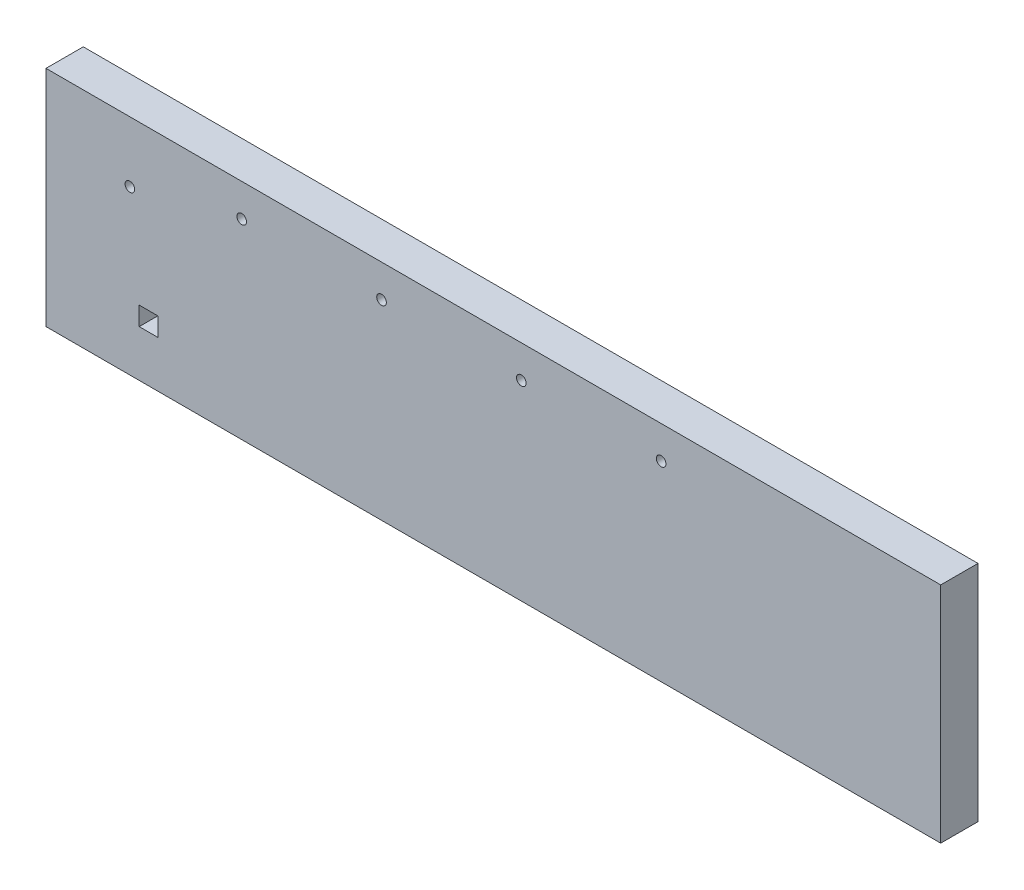
SolidWorks part; units mm, degrees
ref_plane "Front Plane" through (0, 0, 0) normal (0, 0, 1) x (1, 0, 0)
ref_plane "Top Plane" through (0, 0, 0) normal (0, 1, 0) x (1, 0, 0)
ref_plane "Right Plane" through (0, 0, 0) normal (1, 0, 0) x (0, 0, -1)
sketch "Sketch1" plane through (0, 0, 0) normal (0, 0, 1) x (1, 0, 0)
  line L1 (1219.2, 304.8) -> (-1219.2, 304.8)
  line L2 (1219.2, 304.8) -> (1219.2, -304.8)
  line L3 (1219.2, -304.8) -> (-1219.2, -304.8)
  line L4 (-1219.2, 304.8) -> (-1219.2, -304.8)
  line L5 (1219.2, 304.8) -> (-1219.2, -304.8) construction
  line L6 (1219.2, -304.8) -> (-1219.2, 304.8) construction
  line L7 (-965.2, -127) -> (-914.4, -127)
  line L8 (-965.2, -127) -> (-965.2, -177.8)
  line L9 (-965.2, -177.8) -> (-914.4, -177.8)
  line L10 (-914.4, -127) -> (-914.4, -177.8)
  line L11 (-965.2, -127) -> (-914.4, -177.8) construction
  line L12 (-965.2, -177.8) -> (-914.4, -127) construction
  circle A0 centre (-990.6, 139.7) radius 13.1198
  circle A1 centre (-685.8, 215.9) radius 13.1198
  circle A2 centre (-304.8, 215.9) radius 13.1198
  circle A3 centre (76.2, 215.9) radius 13.1198
  circle A4 centre (457.2, 215.9) radius 13.1198
  point P0 (0, 0)
  point P10 (-939.8, -152.4)
  dimension "D10" = 381
  dimension "D11" = 381
  dimension "D12" = 381
  dimension "D1" = 609.6
  dimension "D2" = 2438.4
  dimension "D3" = 88.9
  dimension "D4" = 228.6
  dimension "D5" = 304.8
  dimension "D6" = 165.1
  dimension "D7" = 127
  dimension "D8" = 50.8
  dimension "D9" = 254
extrude "Boss-Extrude1" add sketch "Sketch1" along normal blind 101.6
sketch "Sketch2" plane through (0, 0, 0) normal (0, 0, -1) x (-1, 0, 0)
  line L0 (1219.2, -304.8) -> (-1219.2, -304.8) construction
  line L1 (711.2, -288.925) -> (-711.2, -288.925)
  line L2 (711.2, -288.925) -> (711.2, -273.05)
  line L3 (711.2, -273.05) -> (-711.2, -273.05)
  line L4 (-711.2, -288.925) -> (-711.2, -273.05)
  line L5 (711.2, -288.925) -> (-711.2, -273.05) construction
  line L6 (711.2, -273.05) -> (-711.2, -288.925) construction
  line L7 (1219.2, 304.8) -> (1219.2, -304.8) construction
  line L9 (711.2, -273.05) -> (838.2, -273.05)
  line L10 (711.2, -273.05) -> (711.2, -209.55)
  line L11 (711.2, -209.55) -> (838.2, -209.55)
  line L12 (838.2, -273.05) -> (838.2, -209.55)
  line L13 (711.2, -273.05) -> (838.2, -209.55) construction
  line L14 (711.2, -209.55) -> (838.2, -273.05) construction
  line L15 (838.2, 209.55) -> (711.2, 209.55)
  line L16 (838.2, 209.55) -> (838.2, 273.05)
  line L17 (838.2, 273.05) -> (711.2, 273.05)
  line L18 (711.2, 209.55) -> (711.2, 273.05)
  line L19 (838.2, 209.55) -> (711.2, 273.05) construction
  line L20 (838.2, 273.05) -> (711.2, 209.55) construction
  line L21 (-838.2, -273.05) -> (-711.2, -273.05)
  line L22 (-838.2, -273.05) -> (-838.2, -209.55)
  line L23 (-838.2, -209.55) -> (-711.2, -209.55)
  line L24 (-711.2, -273.05) -> (-711.2, -209.55)
  line L25 (-838.2, -273.05) -> (-711.2, -209.55) construction
  line L26 (-838.2, -209.55) -> (-711.2, -273.05) construction
  line L27 (-711.2, 209.55) -> (-838.2, 209.55)
  line L28 (-711.2, 209.55) -> (-711.2, 273.05)
  line L29 (-711.2, 273.05) -> (-838.2, 273.05)
  line L30 (-838.2, 209.55) -> (-838.2, 273.05)
  line L31 (-711.2, 209.55) -> (-838.2, 273.05) construction
  line L32 (-711.2, 273.05) -> (-838.2, 209.55) construction
  point P0 (0, -280.9875)
  point P9 (774.7, -241.3)
  point P14 (774.7, 241.3)
  point P19 (-774.7, -241.3)
  point P24 (-774.7, 241.3)
  point P29 (711.2, -241.3)
  dimension "D1" = 15.875
  dimension "D2" = 15.875
  dimension "D3" = 508
  dimension "D4" = 1422.4
  dimension "D5" = 95.25
  dimension "D6" = 508
  dimension "D7" = 15.875
  dimension "D8" = 419.1
  dimension "D9" = 15.875
  dimension "D10" = 127
  dimension "D11" = 63.5
  dimension "D12" = 127
  dimension "D13" = 63.5
  dimension "D14" = 63.5
  dimension "D15" = 127
extrude "Cut-Extrude1" cut sketch "Sketch2" against normal blind 50.8 contours L18 L15 L16 L17 | L9 L12 L11 L10 | L30 L27 L28 L29 | L21 L24 L23 L22 region at (774.7, -241.3, 0) region at (-774.7, -241.3, 0) region at (-774.7, 241.3, 0) region at (774.7, 241.3, 0)
sketch "Sketch3" plane through (0, -304.8, 0) normal (0, -1, 0) x (1, 0, 0)
  line L0 (711.2, 0) -> (838.2, 0) construction
  line L1 (838.2, 0) -> (838.2, 50.8) construction
  line L2 (838.2, 50.8) -> (711.2, 50.8) construction
  line L3 (711.2, 50.8) -> (711.2, 0) construction
  line L4 (-838.2, 0) -> (-711.2, 0) construction
  line L5 (-711.2, 0) -> (-711.2, 50.8) construction
  line L6 (-711.2, 50.8) -> (-838.2, 50.8) construction
  line L7 (-838.2, 50.8) -> (-838.2, 0) construction
  line L8 (711.2, 0) -> (838.2, 0)
  line L9 (838.2, 0) -> (838.2, 50.8)
  line L10 (838.2, 50.8) -> (711.2, 50.8)
  line L11 (711.2, 50.8) -> (711.2, 0)
  line L12 (-838.2, 0) -> (-711.2, 0)
  line L13 (-711.2, 0) -> (-711.2, 50.8)
  line L14 (-711.2, 50.8) -> (-838.2, 50.8)
  line L15 (-838.2, 50.8) -> (-838.2, 0)
  line L16 (-838.2, 25.4) -> (-711.2, 25.4) construction
  line L17 (711.2, 25.4) -> (838.2, 25.4) construction
  circle A0 centre (-742.95, 25.4) radius 4.7625
  circle A1 centre (-806.45, 25.4) radius 4.7625
  circle A2 centre (742.95, 25.4) radius 4.7625
  circle A3 centre (806.45, 25.4) radius 4.7625
  point P14 (-774.7, 25.4)
  point P21 (774.7, 25.4)
  dimension "D1" = 9.525
  dimension "D4" = 9.525
  dimension "D2" = 31.75
  dimension "D3" = 31.75
  dimension "D5" = 31.75
  dimension "D6" = 31.75
extrude "Cut-Extrude2" cut sketch "Sketch3" against normal blind 152.4 contours A3 | A2 | A0 | A1 region at (-742.95, -304.8, 25.4) region at (-806.45, -304.8, 25.4) region at (742.95, -304.8, 25.4) region at (806.45, -304.8, 25.4)
